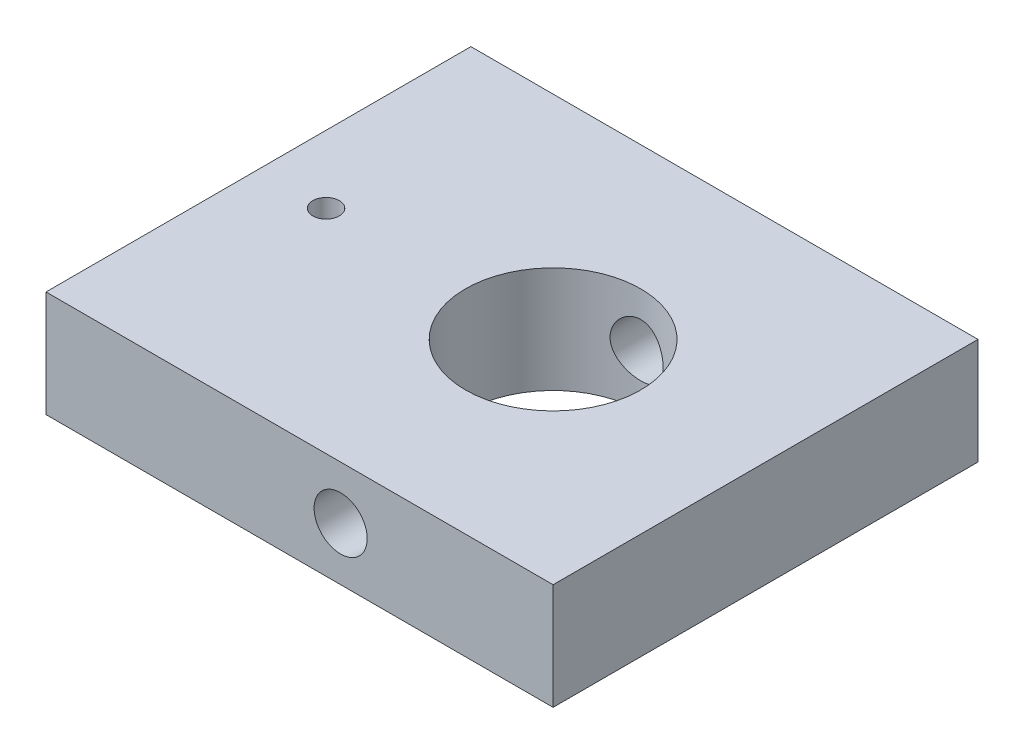
SolidWorks part; units mm, degrees
ref_plane "Front Plane" through (0, 0, 0) normal (0, 0, 1) x (1, 0, 0)
ref_plane "Top Plane" through (0, 0, 0) normal (0, 1, 0) x (1, 0, 0)
ref_plane "Right Plane" through (0, 0, 0) normal (1, 0, 0) x (0, 0, -1)
sketch "Sketch1" plane through (0, 0, 0) normal (0, 1, 0) x (1, 0, 0)
  line L0 (131.445, 50.8) -> (131.445, 0) construction
  line L1 (81.951, 0) -> (203.2, 0)
  line L3 (81.951, 101.6) -> (203.2, 101.6)
  line L4 (203.2, 0) -> (203.2, 101.6)
  line L5 (81.951, 101.6) -> (81.951, 0)
  circle A0 centre (152.4, 50.8) radius 20.955
  circle A2 centre (98.1075, 50.8) radius 3.175
  dimension "D3" = 50.8
  dimension "D4" = 50.8
  dimension "D6" = 41.91
  dimension "D1" = 101.6
  dimension "D2" = 50.8
extrude "Boss-Extrude1" add sketch "Sketch1" along normal blind 25.4
sketch "Sketch2" plane through (0, 0, 0) normal (0, 0, 1) x (1, 0, 0)
  line L0 (81.951, 25.4) -> (203.2, 25.4) construction
  line L1 (203.2, 25.4) -> (203.2, 0) construction
  circle A0 centre (152.4, 12.7) radius 6.35
  dimension "D1" = 12.7
  dimension "D2" = 50.8
extrude "Cut-Extrude1" cut sketch "Sketch2" against normal through all
